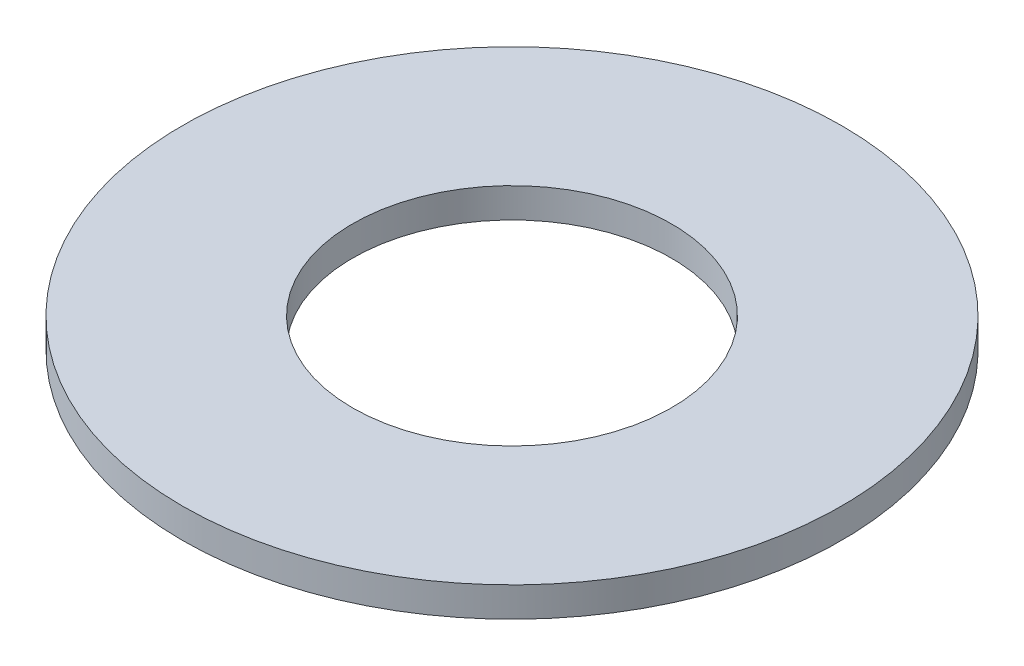
SolidWorks part; units mm, degrees
ref_plane "Front Plane" through (0, 0, 0) normal (0, 0, 1) x (1, 0, 0)
ref_plane "Top Plane" through (0, 0, 0) normal (0, 1, 0) x (1, 0, 0)
ref_plane "Right Plane" through (0, 0, 0) normal (1, 0, 0) x (0, 0, -1)
sketch "Sketch1" plane through (0, 0, 0) normal (0, 1, 0) x (1, 0, 0)
  circle A0 centre (0, 0) radius 77.5
  dimension "FLANGE_OD" = 155
extrude "Boss-Extrude1" add sketch "Sketch1" along normal blind 7
sketch "Sketch2" plane through (0, 0, 0) normal (0, 1, 0) x (1, 0, 0)
  circle A0 centre (0, 0) radius 37.5
  dimension "BORE_D" = 75
extrude "Cut-Extrude1" cut sketch "Sketch2" along normal through all
sketch "Sketch3" plane through (0, 7, 0) normal (0, 1, 0) x (1, 0, 0)
  circle A0 centre (0, 0) radius 31.8271 construction
  circle A1 centre (-31.8271, 0) radius 2.6076
  dimension "BOLT_D" = 5.2152
  dimension "BOLT_PCD" = 63.6542
extrude "Cut-Extrude2" cut sketch "Sketch3" against normal blind 6.4523 rebuild error yes
pattern_circular "CirPattern1" count 8 over 360 rebuild error yes
